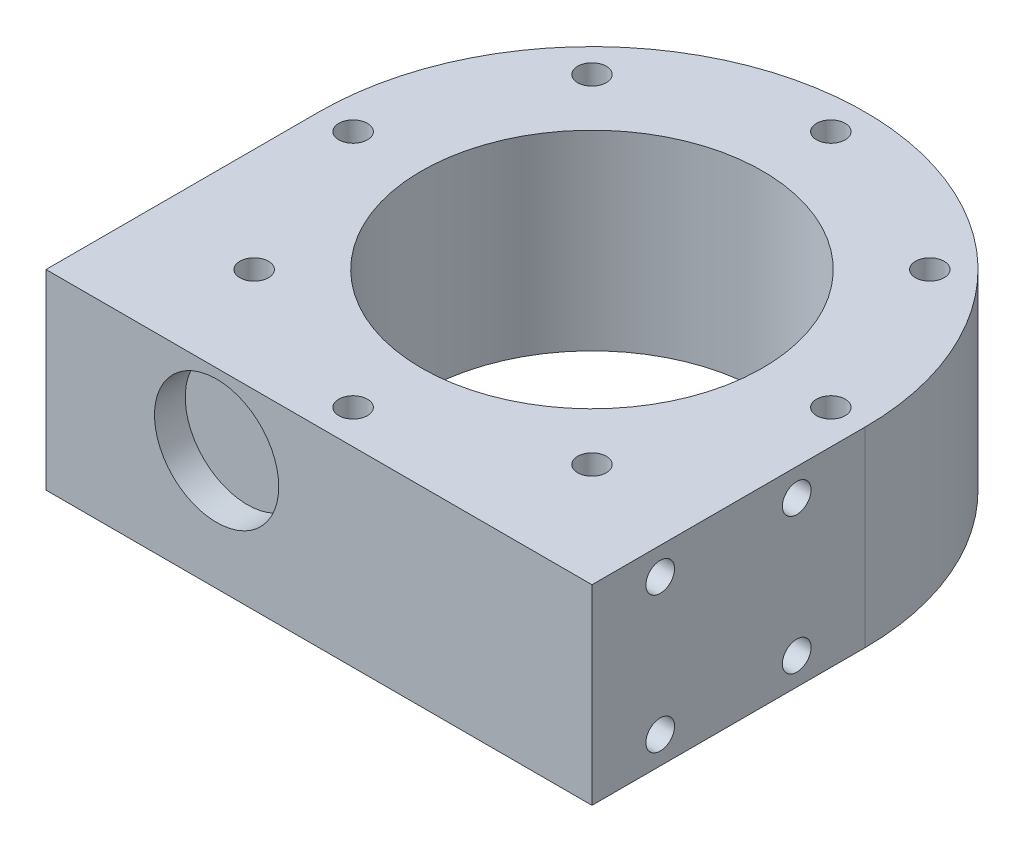
SolidWorks part; units mm, degrees
material "ABS"
ref_plane "前视基准面" through (0, 0, 0) normal (0, 0, 1) x (1, 0, 0)
ref_plane "上视基准面" through (0, 0, 0) normal (0, 1, 0) x (1, 0, 0)
ref_plane "右视基准面" through (0, 0, 0) normal (1, 0, 0) x (0, 0, -1)
other "Configuration Table"
sketch "草图1" plane through (0, 0, 0) normal (0, 1, 0) x (1, 0, 0)
  line L2 (-40, 0) -> (-40, -40)
  line L3 (-40, -40) -> (40, -40)
  line L4 (40, 0) -> (40, -40)
  arc A0 (40, 0) -> (-40, 0) centre (0, 0) ccw
  circle A1 centre (0, 0) radius 25
  dimension "D1" = 80
  dimension "D2" = 50
extrude "凸台-拉伸1" add sketch "草图1" along normal blind 28
sketch "草图2" plane through (0, 28, 0) normal (0, 1, 0) x (1, 0, 0)
  circle A0 centre (0, 0) radius 35 construction
  circle A1 centre (0, 35) radius 2.1
  circle A2 centre (24.7487, 24.7487) radius 2.1
  circle A3 centre (35, 0) radius 2.1
  circle A4 centre (24.7487, -24.7487) radius 2.1
  circle A5 centre (0, -35) radius 2.1
  circle A6 centre (-24.7487, -24.7487) radius 2.1
  circle A7 centre (-35, 0) radius 2.1
  circle A8 centre (-24.7487, 24.7487) radius 2.1
  point P21 (0, 0)
  dimension "D1" = 70
  dimension "D2" = 4.2
  dimension "D3" = 8
extrude "切除-拉伸1" cut sketch "草图2" against normal through all
sketch "草图6" plane through (0, 0, 40) normal (0, 0, 1) x (1, 0, 0)
  line L0 (-40, 28) -> (-40, 0) construction
  line L1 (-40, 0) -> (40, 0) construction
  circle A0 centre (-15, 17.5) radius 9.1
  dimension "D1" = 18.2
  dimension "D2" = 25
  dimension "D3" = 17.5
extrude "切除-拉伸2" cut sketch "草图6" against normal blind 4.5
sketch "草图7" plane through (-40, 0, 0) normal (-1, 0, 0) x (0, 0, 1)
  line L0 (20, 28) -> (20, 0) construction
  line L1 (0, 28) -> (40, 28) construction
  line L2 (0, 0) -> (40, 0) construction
  line L4 (10, 24) -> (30, 24) construction
  line L5 (10, 24) -> (10, 4) construction
  line L6 (10, 4) -> (30, 4) construction
  line L7 (30, 24) -> (30, 4) construction
  line L8 (20, 4) -> (20, 24) construction
  line L9 (10, 14) -> (30, 14) construction
  circle A0 centre (10, 24) radius 2.1
  circle A1 centre (30, 24) radius 2.1
  circle A2 centre (10, 4) radius 2.1
  circle A3 centre (30, 4) radius 2.1
  point P6 (20, 14)
  dimension "D3" = 4.2
  dimension "D1" = 20
  dimension "D2" = 20
extrude "切除-拉伸3" cut sketch "草图7" against normal blind 4
ref_plane "基准面1" through (0, 0, 0) normal (-1, 0, 0) x (0, 0, 1)
mirror "镜向1" about plane through (0, 0, 0) normal (-1, 0, 0) of "切除-拉伸3"
